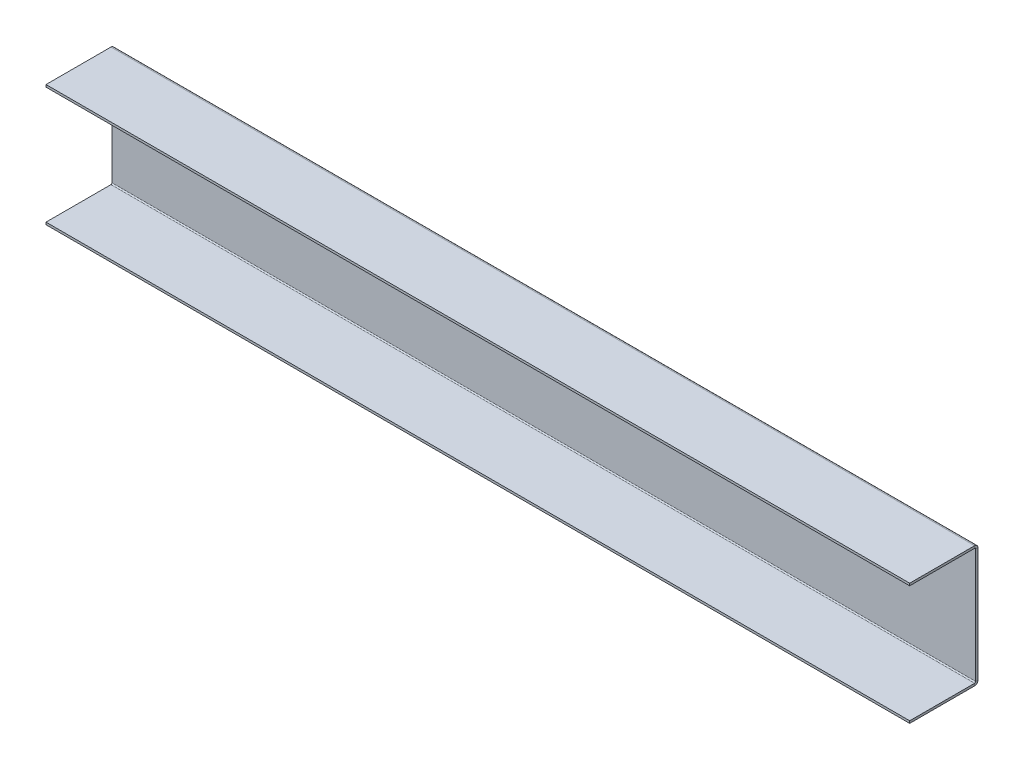
SolidWorks part; units mm, degrees
note: The reader was unsure of these and kept them because the rebuilt part matched: flange length of "Ребро-кромка1".
ref_plane "Спереди" through (0, 0, 0) normal (0, 0, 1) x (1, 0, 0)
ref_plane "Сверху" through (0, 0, 0) normal (0, 1, 0) x (1, 0, 0)
ref_plane "Справа" through (0, 0, 0) normal (1, 0, 0) x (0, 0, -1)
sketch "Эскиз1" plane through (0, 0, 0) normal (0, 0, 1) x (1, 0, 0)
  line L1 (-284.5, -40) -> (284.5, -40)
  line L2 (-284.5, -40) -> (-284.5, 40)
  line L3 (-284.5, 40) -> (284.5, 40)
  line L4 (284.5, -40) -> (284.5, 40)
  line L5 (-284.5, -40) -> (284.5, 40) construction
  line L6 (-284.5, 40) -> (284.5, -40) construction
  point P0 (0, 0)
  dimension "D1" = 80
  dimension "D2" = 569
base flange "Базовая кромка1" sketch "Эскиз1" thickness 1.5 reverse thickness direction no parameters "D1"=0.7366
edge flange "Ребро-кромка1" sketch "Эскиз5" flange profiles "Эскиз5", "Эскиз7" flange angle 90 flange length 45 flange position material inside bend radius 0.7366 thickness 1.5 relief rectangular parameters "D6"=10, "D8"=1
sketch "Эскиз5" plane through (0, 40, 0) normal (0, 1, 0) x (-1, 0, 0)
  line L0 (-284.5, 0) -> (284.5, 0) construction
  line L1 (-284.5, 0) -> (284.5, 0)
  line L2 (-284.5, 0) -> (-284.5, 43.5)
  line L3 (-284.5, 43.5) -> (284.5, 43.5)
  line L4 (284.5, 43.5) -> (284.5, 0)
sketch "Эскиз7" plane through (0, -40, 0) normal (0, -1, 0) x (1, 0, 0)
  line L0 (-284.5, 0) -> (284.5, 0) construction
  line L1 (-284.5, 0) -> (284.5, 0)
  line L2 (-284.5, 0) -> (-284.5, 43.5)
  line L3 (-284.5, 43.5) -> (284.5, 43.5)
  line L4 (284.5, 43.5) -> (284.5, 0)
bend "EdgeBend1" bend radius 0.7366 bend angle 90 parameters "D5"=1
bend "EdgeBend2" bend radius 0.7366 bend angle 90 parameters "D5"=3
sketch "Сгиб-Линии1" [suppressed] plane through (0, 0, 0) normal (0, 1, 0) x (1, 0, 0)
sketch "Граничная рамка1" [suppressed] plane through (0, 0, 0) normal (0, 1, 0) x (1, 0, 0)
sheet metal parameters "Листовой металл3" thickness 1.5 parameters "D1"=0.7366
flat pattern "Развертка3" [suppressed]
sketch "Сгиб-Линии2" plane through (0, 0, 0) normal (0, 1, 0) x (1, 0, 0)
sketch "Граничная рамка2" [suppressed] plane through (0, 0, 0) normal (0, 1, 0) x (1, 0, 0)
sheet metal parameters "Листовой металл7" thickness 1.5 parameters "D1"=0.7366
flat pattern "Развертка3"
sketch "Сгиб-Линии2" plane through (0, 0, 0) normal (0, 0, 1) x (1, 0, 0)
  line L0 (-287.5, -38.8132) -> (287.5, -38.8132) construction
  line L1 (287.5, 38.8132) -> (-287.5, 38.8132) construction
  line L2 (-287.5, -38.8132) -> (287.5, -38.8132) construction
  line L3 (287.5, 38.8132) -> (-287.5, 38.8132) construction
sketch3d "Граничная рамка2" [suppressed]
  line L0 (-287.5, -82.6263, 0) -> (287.5, -82.6263, 0) construction
  line L1 (-287.5, 82.6263, 0) -> (287.5, 82.6263, 0) construction
  line L2 (-287.5, -82.6263, 0) -> (-287.5, 82.6263, 0) construction
  line L3 (287.5, -82.6263, 0) -> (287.5, 82.6263, 0) construction
bend of the flat pattern "Плоское состояние-<EdgeBend1>1"
bend of the flat pattern "Плоское состояние-<EdgeBend2>1"
